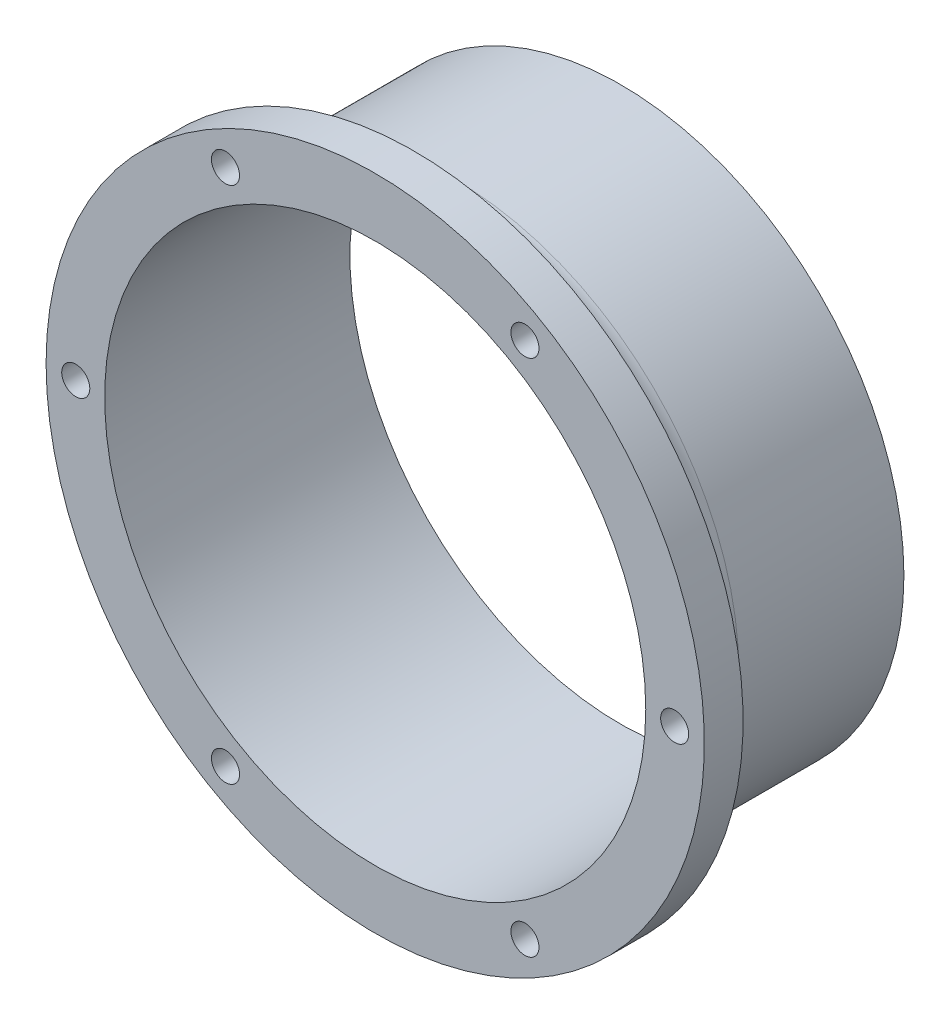
SolidWorks part; units mm, degrees
material "6061-T6 (SS)"
ref_plane "Front Plane" through (0, 0, 0) normal (0, 0, 1) x (1, 0, 0)
ref_plane "Top Plane" through (0, 0, 0) normal (0, 1, 0) x (1, 0, 0)
ref_plane "Right Plane" through (0, 0, 0) normal (1, 0, 0) x (0, 0, -1)
sketch "Sketch1" plane through (0, 0, 0) normal (0, 0, 1) x (1, 0, 0)
  circle A0 centre (0, 0) radius 34.8615
  circle A1 centre (0, 0) radius 33.274
  dimension "D1" = 69.723
  dimension "D2" = 1.5875
extrude "Boss-Extrude1" add sketch "Sketch1" along normal blind 25.4
sketch "Sketch2" plane through (0, 0, 25.4) normal (0, 0, 1) x (1, 0, 0)
  circle A0 centre (0, 0) radius 33.274
  circle A1 centre (0, 0) radius 40.4813
  circle A2 centre (0, 0) radius 33.274 construction
  dimension "D1" = 80.9625
extrude "Boss-Extrude2" add sketch "Sketch2" along normal blind 4.7625
fillet "Fillet1" radius 5.08 1 edges at (34.8615, 0, 25.4)
sketch "Sketch3" plane through (0, 0, 30.1625) normal (0, 0, 1) x (1, 0, 0)
  circle A0 centre (0, 0) radius 35.56
  dimension "D1" = 71.12
sketch "Sketch4" plane through (0, 0, 30.1625) normal (0, 0, 1) x (1, 0, 0)
  circle A0 centre (0, 0) radius 36.83 construction
  dimension "D1" = 73.66
hole_wizard "#8-32 Tapped Hole1" positions "Sketch6" profile "Sketch7" tap size "#8-32" standard "Ansi Inch"
sketch "Sketch6" plane through (0, 0, 30.1625) normal (0, 0, 1) x (1, 0, 0)
  line L0 (0, 0) -> (0, 47.1812) construction
  line L2 (0, 0) -> (-18.415, 31.8957) construction
  circle A0 centre (0, 0) radius 36.83 construction
  point P0 (-18.415, 31.8957)
  dimension "D1" = 30
sketch "Sketch7" plane through (-18.415, 31.8957, 30.1625) normal (1, 0, 0) x (0, -1, 0)
  line L0 (0, 0) -> (0, 11.7058)
  line L1 (0, 11.7058) -> (1.7272, 10.668)
  line L2 (1.7272, 10.668) -> (1.7272, 0)
  line L5 (1.7272, 0) -> (0, 0)
  line L10 (0, 11.7058) -> (-1.7272, 10.668) construction
  line L11 (0, -6.35) -> (0, 107.95) construction
  dimension "Tap Drill Dia." = 3.4544
  dimension "Tap Drill Depth" = 10.668
  dimension "Drill Angle" = 118
cosmetic thread "Hole Thread1" parameters "D1"=8.382, "D2"=4.1656
pattern_circular "CirPattern1" count 6 over 360 about axis through (0, 0, 30.1625) along (0, 0, 1) of "#8-32 Tapped Hole1"
